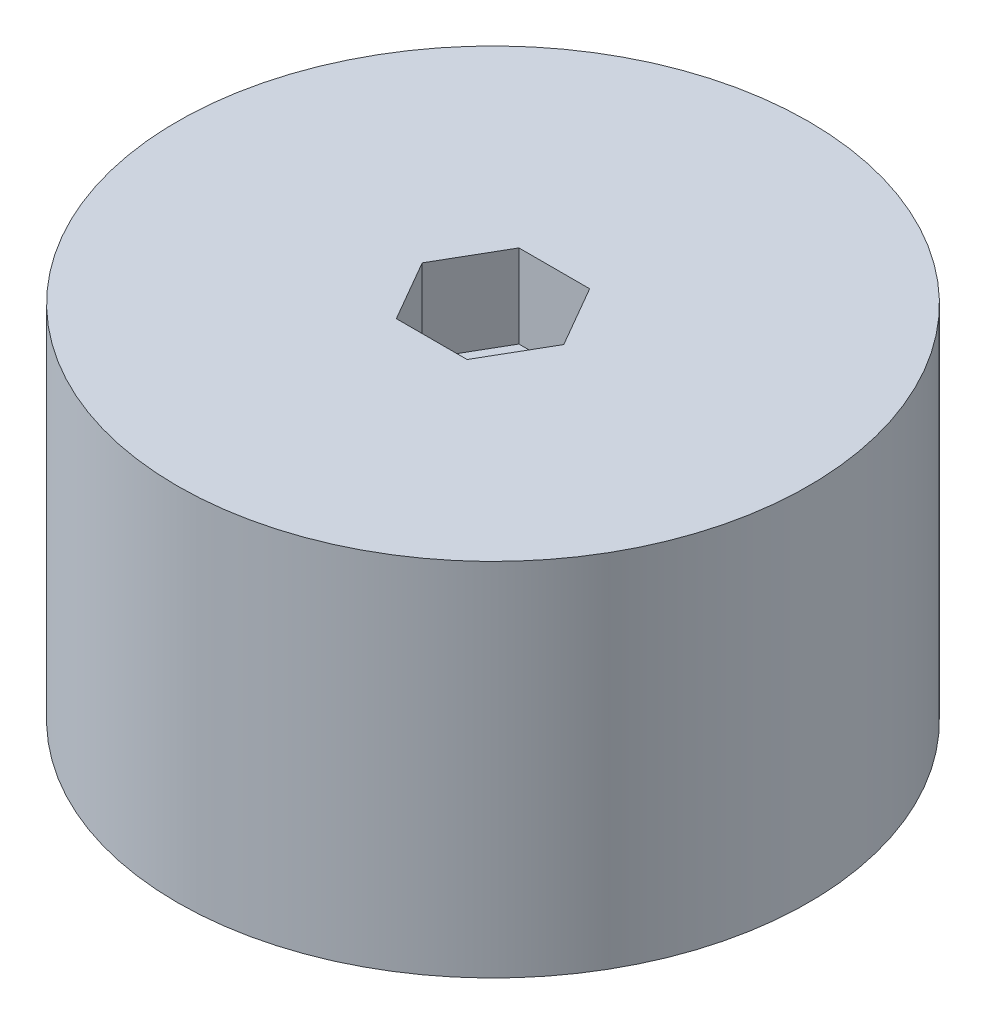
SolidWorks part; units mm, degrees
ref_plane "Front Plane" through (0, 0, 0) normal (0, 0, 1) x (1, 0, 0)
ref_plane "Top Plane" through (0, 0, 0) normal (0, 1, 0) x (1, 0, 0)
ref_plane "Right Plane" through (0, 0, 0) normal (1, 0, 0) x (0, 0, -1)
sketch "Sketch1" plane through (0, 0, 0) normal (0, 1, 0) x (1, 0, 0)
  circle A0 centre (0, 0) radius 22.75
  circle A1 centre (0, 0) radius 2.15
  dimension "D1" = 45.5
  dimension "D2" = 4.3
extrude "Boss-Extrude1" add sketch "Sketch1" along normal blind 26
sketch "Sketch2" plane through (0, 26, 0) normal (0, 1, 0) x (1, 0, 0)
  line L1 (5.1, 0) -> (2.55, 4.4167)
  line L2 (2.55, 4.4167) -> (-2.55, 4.4167)
  line L3 (-2.55, 4.4167) -> (-5.1, 0)
  line L4 (-5.1, 0) -> (-2.55, -4.4167)
  line L5 (-2.55, -4.4167) -> (2.55, -4.4167)
  line L6 (2.55, -4.4167) -> (5.1, 0)
  circle A0 centre (0, 0) radius 4.4167 construction
  dimension "D1" = 5.1
extrude "Cut-Extrude1" cut sketch "Sketch2" against normal blind 6
